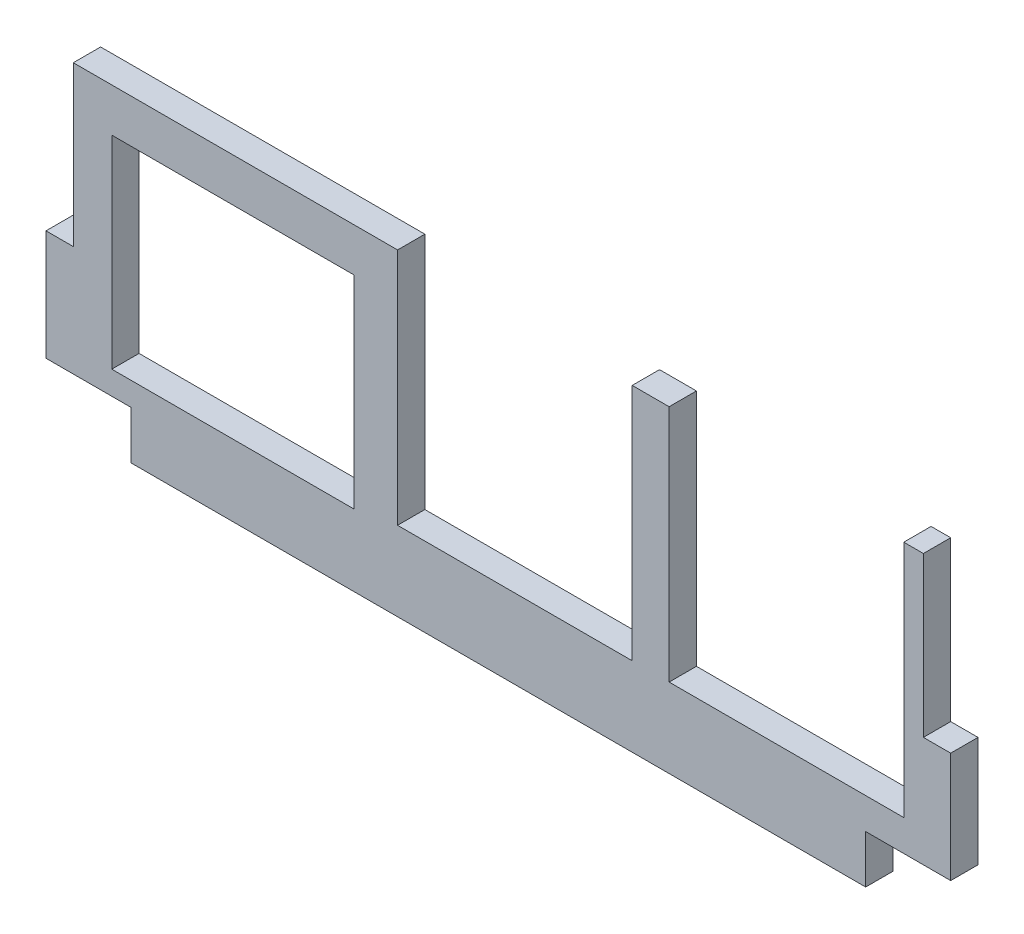
SolidWorks part; units mm, degrees
ref_plane "Front Plane" through (0, 0, 0) normal (0, 0, 1) x (1, 0, 0)
ref_plane "Top Plane" through (0, 0, 0) normal (0, 1, 0) x (1, 0, 0)
ref_plane "Right Plane" through (0, 0, 0) normal (1, 0, 0) x (0, 0, -1)
sketch "Sketch1" plane through (0, 0, 0) normal (0, 0, 1) x (1, 0, 0)
  line L0 (-1.8034, 12.0142) -> (0, 12.0142) construction
  line L1 (-1.8034, 12.0142) -> (-1.8034, 4.7244) construction
  line L2 (3.81, 1.5494) -> (3.81, 4.7244) construction
  line L3 (3.81, 1.5494) -> (52.324, 1.5494) construction
  line L4 (52.324, 1.5494) -> (52.324, 4.7244) construction
  line L5 (57.9374, 12.0142) -> (56.134, 12.0142) construction
  line L6 (57.9374, 4.7244) -> (57.9374, 12.0142) construction
  line L7 (-1.8034, 12.0142) -> (0, 12.0142)
  line L8 (-1.8034, 12.0142) -> (-1.8034, 4.7244)
  line L9 (3.81, 1.5494) -> (3.81, 4.7244)
  line L10 (3.81, 1.5494) -> (52.324, 1.5494)
  line L11 (52.324, 1.5494) -> (52.324, 4.7244)
  line L12 (57.9374, 12.0142) -> (56.134, 12.0142)
  line L13 (57.9374, 4.7244) -> (57.9374, 12.0142)
  line L14 (-1.8034, 4.7244) -> (3.81, 4.7244)
  line L15 (52.324, 4.7244) -> (57.9374, 4.7244)
  line L16 (0, 12.0142) -> (0, 19.6596)
  line L17 (0, 27.2034) -> (0, 4.7244) construction
  line L18 (0, 19.6596) -> (2.54, 19.6596)
  line L19 (2.54, 19.6596) -> (2.54, 6.2738)
  line L20 (2.54, 6.2738) -> (18.542, 6.2738)
  line L21 (18.542, 6.2738) -> (18.542, 22.5298)
  line L22 (18.542, 22.5298) -> (21.4122, 22.5298)
  line L23 (21.4122, 22.5298) -> (21.4122, 6.7818)
  line L24 (21.4122, 6.7818) -> (36.9062, 6.7818)
  line L25 (36.9062, 6.7818) -> (36.9062, 22.5298)
  line L26 (36.9062, 22.5298) -> (39.3446, 22.5298)
  line L27 (39.3446, 22.5298) -> (39.3446, 6.7818)
  line L28 (39.3446, 6.7818) -> (54.8386, 6.7818)
  line L29 (54.8386, 6.7818) -> (54.8386, 22.5298)
  line L30 (54.8386, 22.5298) -> (56.134, 22.5298)
  line L31 (56.134, 27.2034) -> (56.134, 4.7244) construction
  line L32 (56.134, 22.5298) -> (56.134, 12.0142)
  dimension "D1" = 14.9352
  dimension "D2" = 2.54
  dimension "D3" = 2.8702
  dimension "D4" = 2.4384
  dimension "D5" = 15.494
  dimension "D6" = 16.002
  dimension "D7" = 1.5494
  dimension "D8" = 15.748
  dimension "D9" = 2.0574
extrude "Boss-Extrude1" add sketch "Sketch1" along normal blind 1.8034
sketch "Sketch2" plane through (0, 0, 1.8034) normal (0, 0, 1) x (1, 0, 0)
  line L1 (0, 19.6596) -> (18.542, 19.6596)
  line L2 (0, 19.6596) -> (0, 22.5298)
  line L3 (0, 22.5298) -> (18.542, 22.5298)
  line L4 (18.542, 19.6596) -> (18.542, 22.5298)
extrude "Boss-Extrude2" add sketch "Sketch2" against normal up to vertex (1.8034 mm away) up to point (18.542, 22.5298, 0)
